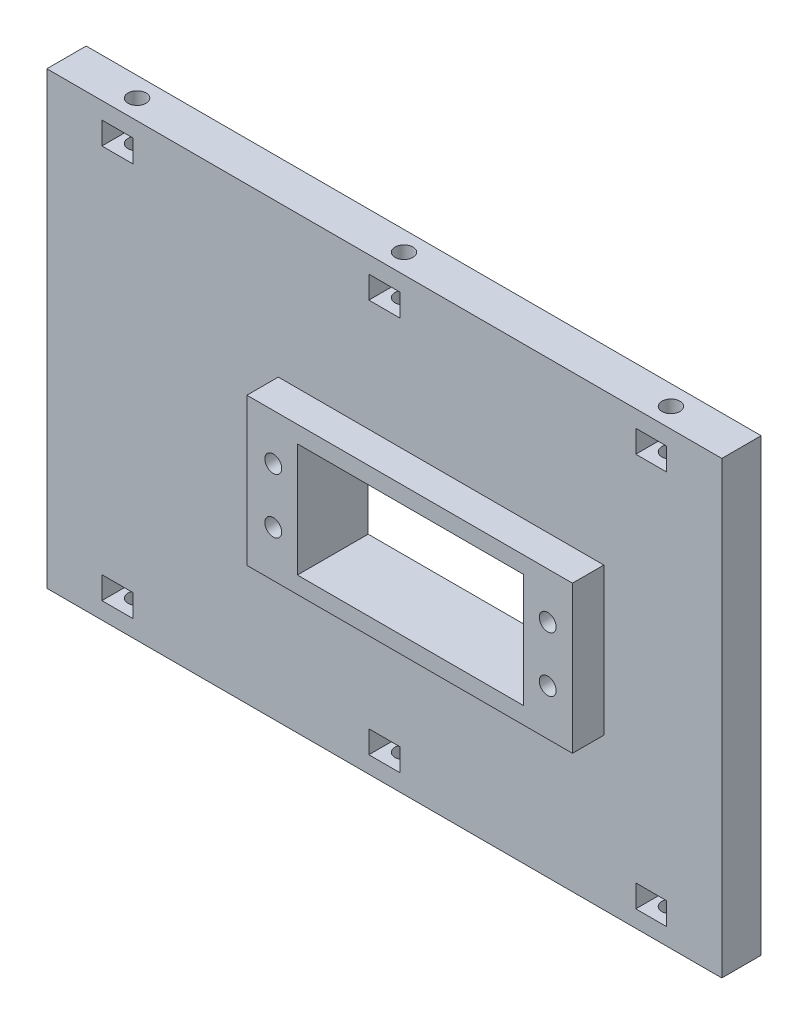
SolidWorks part; units mm, degrees
ref_plane "Plano frontal" through (0, 0, 0) normal (0, 0, 1) x (1, 0, 0)
ref_plane "Plano superior" through (0, 0, 0) normal (0, 1, 0) x (1, 0, 0)
ref_plane "Plano direito" through (0, 0, 0) normal (1, 0, 0) x (0, 0, -1)
sketch "Esboço1" plane through (0, 0, 0) normal (0, 0, 1) x (1, 0, 0)
  line L0 (-50.21, -37) -> (-60, -37) construction
  line L5 (-60, 40) -> (60, 40)
  line L6 (-60, 40) -> (-60, -40)
  line L8 (-60, -40) -> (60, -40)
  line L10 (-18.85, 0) -> (-29.82, 0) construction
  line L11 (60, 40) -> (60, -40)
  line L31 (0.18, 0) -> (34.63, 0) construction
  line L36 (34.63, 0) -> (34.63, 10.1) construction
  line L37 (34.63, 10.1) -> (30.33, 10.1) construction
  line L38 (34.63, 0) -> (34.63, -4.9) construction
  line L39 (30.33, 10.1) -> (-9.87, 10.1)
  line L40 (30.33, 10.1) -> (30.33, -10.1)
  line L41 (30.33, -10.1) -> (-9.87, -10.1)
  line L42 (-9.87, 10.1) -> (-9.87, -10.1)
  line L43 (-60, 40) -> (60, -40) construction
  line L44 (-60, -40) -> (60, 40) construction
  line L45 (-14.17, 4.9) -> (-18.67, 4.9) construction
  line L76 (34.63, 4.9) -> (39.21, 4.9) construction
  line L112 (-7.0787, 10.1) -> (-7.0787, 13.1) construction
  line L113 (-2.2667, -10.1) -> (-2.2667, -13.1) construction
  line L116 (-18.85, 13.1) -> (39.03, 13.1)
  line L117 (-18.85, 13.1) -> (-18.85, -13.1)
  line L118 (-18.85, -13.1) -> (39.03, -13.1)
  line L119 (39.03, 13.1) -> (39.03, -13.1)
  line L125 (-50.21, -40) -> (-50.21, -37) construction
  line L126 (0, 0) -> (0, -40) construction
  line L127 (-50.21, -37) -> (-44.71, -37)
  line L128 (-50.21, -37) -> (-50.21, -33)
  line L129 (-50.21, -33) -> (-44.71, -33)
  line L130 (-44.71, -37) -> (-44.71, -33)
  line L132 (50.21, -37) -> (50.21, -33)
  line L133 (50.21, -33) -> (44.71, -33)
  line L134 (44.71, -37) -> (44.71, -33)
  line L135 (50.21, -37) -> (44.71, -37)
  line L136 (-50.21, -37) -> (-44.71, -33) construction
  line L138 (-47.46, -35) -> (50.21, -35) construction
  line L139 (34.63, 0) -> (60, 0) construction
  line L140 (-2.75, -33) -> (2.75, -33)
  line L141 (-2.75, -33) -> (-2.75, -37)
  line L142 (-2.75, -37) -> (2.75, -37)
  line L143 (2.75, -33) -> (2.75, -37)
  line L144 (-2.75, -33) -> (2.75, -37) construction
  line L145 (-2.75, -37) -> (2.75, -33) construction
  line L146 (50.21, 37) -> (44.71, 37)
  line L147 (44.71, 37) -> (44.71, 33)
  line L148 (50.21, 33) -> (44.71, 33)
  line L149 (50.21, 37) -> (50.21, 33)
  line L150 (-2.75, 37) -> (2.75, 37)
  line L151 (2.75, 33) -> (2.75, 37)
  line L152 (-2.75, 33) -> (2.75, 33)
  line L153 (-2.75, 33) -> (-2.75, 37)
  line L154 (-50.21, 37) -> (-50.21, 33)
  line L155 (-50.21, 33) -> (-44.71, 33)
  line L156 (-44.71, 37) -> (-44.71, 33)
  line L157 (-50.21, 37) -> (-44.71, 37)
  circle A0 centre (34.63, -4.9) radius 1.5016
  circle A1 centre (34.63, 4.9) radius 1.5016
  circle A2 centre (-14.17, -4.9) radius 1.5016
  circle A3 centre (-14.17, 4.9) radius 1.5016
  point P0 (0, 0)
  point P1 (0, 0)
  point P22 (0, -35)
  point P35 (0, 0)
  dimension "D12" = 3.0033
  dimension "D3" = 120
  dimension "D4" = 80
  dimension "D5" = 5.5
  dimension "D6" = 34.45
  dimension "D7" = 4.3
  dimension "D8" = 10.1
  dimension "D9" = 40.2
  dimension "D10" = 20.2
  dimension "D11" = 4.9
  dimension "D13" = 3
  dimension "D14" = 4.5
  dimension "D15" = 10.97
  dimension "D16" = 4
  dimension "D17" = 5.5
  dimension "D18" = 4
  dimension "D19" = 3
  dimension "D20" = 4.58
  dimension "D21" = 3
extrude "Ressalto-extrusão4" add sketch "Esboço1" along normal blind 7 contours L143 L140 L141 L142 | L135 L132 L133 L134 | L157 L154 L155 L156 | L153 L152 L151 L150 | L149 L146 L147 L148 | L39 L42 L41 L40 | A3 | A2 | A1 | A0 | L6 L5 L11 L8 | L127 L130 L129 L128 region at (10.23, 0, 0) region at (47.46, -35, 0) region at (0, -35, 0) region at (47.46, 35, 0) region at (0, 35, 0) region at (-47.46, 35, 0) region at (34.63, -4.9, 0) region at (34.63, 4.9, 0) region at (-14.17, -4.9, 0) region at (-14.17, 4.9, 0)
extrude "Ressalto-extrusão5" add sketch "Esboço1<12>" along normal blind 5.58 from surface contours L119 L116 L117 L118 A3 A1 A0 L42 L39 L40 L41 A2 region at (10.09, 12.4647, 0) starting at face at (-47.46, -35, 7)
sketch "Esboço1<12>" plane through (0, 0, 0) normal (0, 0, 1) x (1, 0, 0) same geometry as "Esboço1"
sketch "Esboço9" plane through (0, -40, 0) normal (0, -1, 0) x (1, 0, 0)
  line L0 (-60, 3.5) -> (-47.46, 3.5) construction
  line L1 (-60, 7) -> (-60, 0) construction
  line L2 (0, 0) -> (0, 7) construction
  line L3 (-60, 0) -> (60, 0) construction
  line L4 (-60, 7) -> (60, 7) construction
  circle A0 centre (-47.46, 3.5) radius 1.6
  circle A1 centre (0, 3.5) radius 1.6
  circle A2 centre (47.46, 3.5) radius 1.6
  dimension "D2" = 3.2
  dimension "D3" = 3.2
  dimension "D1" = 12.54
extrude "Corte-extrusão7" cut sketch "Esboço9" against normal blind 10
sketch "Esboço10" plane through (0, 40, 0) normal (0, 1, 0) x (1, 0, 0)
  line L0 (-60, -3.5) -> (-47.46, -3.5) construction
  line L1 (-60, -7) -> (-60, 0) construction
  line L2 (0, 0) -> (0, -7) construction
  line L3 (-60, 0) -> (60, 0) construction
  line L4 (-60, -7) -> (60, -7) construction
  circle A0 centre (-47.46, -3.5) radius 1.6
  circle A1 centre (0, -3.5) radius 1.6
  circle A2 centre (47.46, -3.5) radius 1.6
  dimension "D2" = 3.2
  dimension "D3" = 3.2
  dimension "D1" = 12.54
extrude "Corte-extrusão8" cut sketch "Esboço10" against normal blind 10
